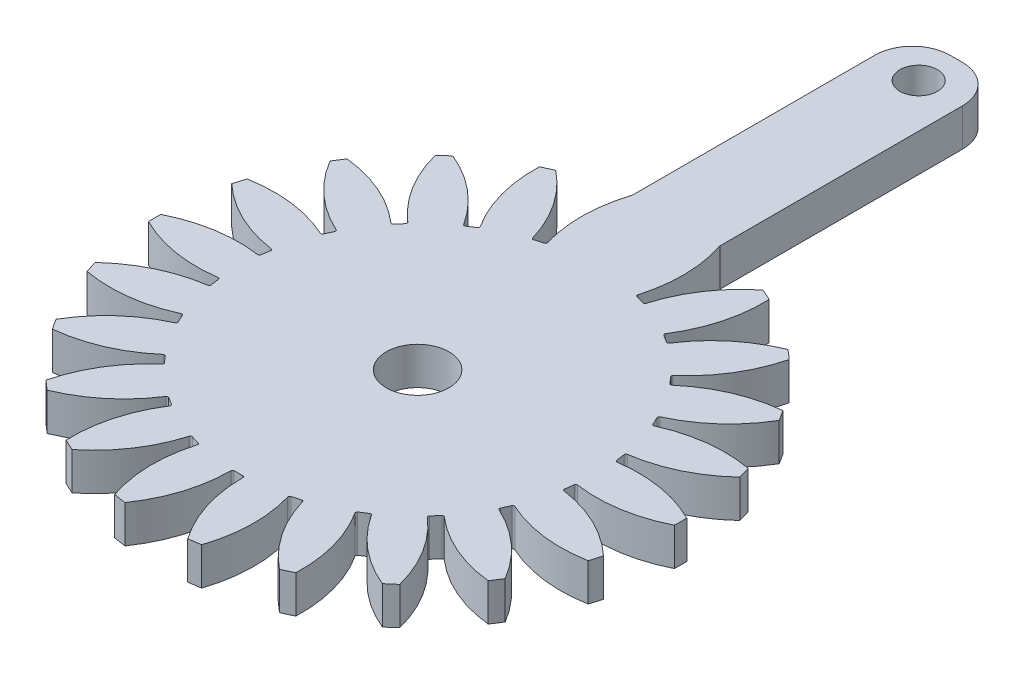
SolidWorks part; units mm, degrees
material "Nickel"
ref_plane "Front Plane" through (0, 0, 0) normal (0, 0, 1) x (1, 0, 0)
ref_plane "Top Plane" through (0, 0, 0) normal (0, 1, 0) x (1, 0, 0)
ref_plane "Right Plane" through (0, 0, 0) normal (1, 0, 0) x (0, 0, -1)
sketch "Sketch1" plane through (0, 0, 0) normal (0, 1, 0) x (1, 0, 0)
  circle A0 centre (0, 0) radius 21
  dimension "D1" = 42
extrude "Boss-Extrude1" add sketch "Sketch1" along normal blind 3
sketch "Sketch2" plane through (0, 3, 0) normal (0, 1, 0) x (1, 0, 0)
  circle A0 centre (0, 0) radius 2.5
  dimension "D1" = 5
extrude "Cut-Extrude1" cut sketch "Sketch2" against normal through all both and the other way through all
sketch "Sketch3" plane through (0, 3, 0) normal (0, 1, 0) x (1, 0, 0)
  line L0 (0, 0) -> (0, 21) construction
  line L1 (0.35, 14.3) -> (-0.35, 14.3)
  circle A0 centre (0, 0) radius 21 construction
  arc A3 (-2.5, 20.8507) -> (2.5, 20.8507) centre (0, 0) cw
  arc A6 (-0.35, 14.3) -> (-0.4765, 14.4265) centre (-0.35, 14.4265) cw
  arc A7 (-0.4765, 14.4265) -> (-2.5, 20.8507) centre (-11.6858, 14.4265) ccw
  arc A8 (0.35, 14.3) -> (0.4765, 14.4265) centre (0.35, 14.4265) ccw
  arc A9 (0.4765, 14.4265) -> (2.5, 20.8507) centre (11.6858, 14.4265) cw
  point P21 (0, 21)
  point P22 (0, 14.3)
  dimension "D4" = 6.7
  dimension "D1" = 5
  dimension "D2" = 0.7
extrude "Cut-Extrude2" cut sketch "Sketch3" against normal through all both and the other way through all
pattern_circular "CirPattern1" count 22 over 360 about axis through (0, 0, 0) along (0, 1, 0) of "Cut-Extrude2" reverse direction yes
sketch "Sketch4" plane through (0, 3, 0) normal (0, 1, 0) x (1, 0, 0)
  line L0 (0, 27.75) -> (0, 0) construction
  line L1 (-3.5, 43) -> (3.5, 43)
  line L2 (-3.5, 43) -> (-3.5, 12.5)
  line L3 (-3.5, 12.5) -> (3.5, 12.5)
  line L4 (3.5, 43) -> (3.5, 12.5)
  line L5 (-3.5, 43) -> (3.5, 12.5) construction
  line L6 (-3.5, 12.5) -> (3.5, 43) construction
  point P0 (0, 27.75)
  dimension "D1" = 7
  dimension "D2" = 30.5
  dimension "D3" = 12.5
extrude "Boss-Extrude2" add sketch "Sketch4" against normal blind 3
fillet "Fillet1" radius 3 2 edges at (3.5, 1.5, -43) (-3.5, 1.5, -43)
sketch "Sketch5" plane through (0, 3, 0) normal (0, 1, 0) x (1, 0, 0)
  line L0 (0, 43) -> (0, 40) construction
  line L1 (0.5, 43) -> (-0.5, 43) construction
  circle A0 centre (0, 40) radius 1.5
  dimension "D2" = 3
  dimension "D1" = 3
extrude "Cut-Extrude3" cut sketch "Sketch5" against normal through all both and the other way through all
sketch "Sketch6" plane through (0, 3, 0) normal (0, 1, 0) x (1, 0, 0)
  line L0 (0.5, 43) -> (-0.5, 43) construction
  line L1 (0, 0) -> (0, 43) construction
